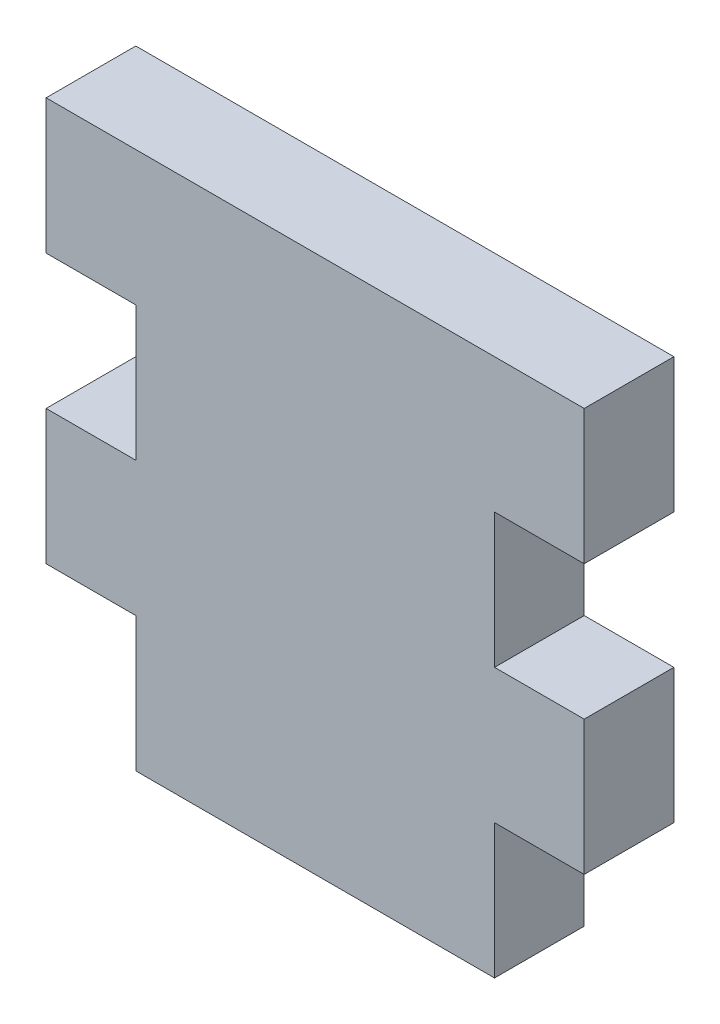
SolidWorks part; units mm, degrees
ref_plane "Front Plane" through (0, 0, 0) normal (0, 0, 1) x (1, 0, 0)
ref_plane "Top Plane" through (0, 0, 0) normal (0, 1, 0) x (1, 0, 0)
ref_plane "Right Plane" through (0, 0, 0) normal (1, 0, 0) x (0, 0, -1)
sketch "Sketch1" plane through (0, 0, 0) normal (0, 0, 1) x (1, 0, 0)
  line L1 (-88.0852, 14.1109) -> (-49.9852, 14.1109)
  line L2 (-88.0852, 14.1109) -> (-88.0852, -23.9891)
  line L3 (-88.0852, -23.9891) -> (-49.9852, -23.9891)
  line L4 (-49.9852, 14.1109) -> (-49.9852, -23.9891)
  dimension "D1" = 38.1
  dimension "D2" = 38.1
extrude "Boss-Extrude1" add sketch "Sketch1" along normal blind 6.35
sketch "Sketch2" plane through (0, 0, 6.35) normal (0, 0, 1) x (1, 0, 0)
  line L0 (-88.0852, 14.1109) -> (-88.0852, -23.9891) construction
  line L1 (-88.0852, -23.9891) -> (-81.7352, -23.9891)
  line L2 (-88.0852, -23.9891) -> (-88.0852, -14.4641)
  line L3 (-88.0852, -14.4641) -> (-81.7352, -14.4641)
  line L4 (-81.7352, -23.9891) -> (-81.7352, -14.4641)
  line L5 (-88.0852, -4.9391) -> (-81.7352, -4.9391)
  line L6 (-88.0852, -4.9391) -> (-88.0852, 4.5859)
  line L7 (-88.0852, 4.5859) -> (-81.7352, 4.5859)
  line L8 (-81.7352, -4.9391) -> (-81.7352, 4.5859)
  line L9 (-81.7352, 4.5859) -> (-81.7352, 14.1109) construction
  line L10 (-49.9852, 14.1109) -> (-88.0852, 14.1109) construction
  line L11 (-81.7352, -4.9391) -> (-81.7352, -14.4641) construction
  line L12 (-69.0352, 14.1109) -> (-69.0352, -23.9891) construction
  line L13 (-88.0852, -23.9891) -> (-49.9852, -23.9891) construction
  line L14 (-56.3352, -4.9391) -> (-56.3352, -14.4641) construction
  line L15 (-56.3352, 4.5859) -> (-56.3352, 14.1109) construction
  line L16 (-56.3352, -4.9391) -> (-56.3352, 4.5859)
  line L17 (-49.9852, 4.5859) -> (-56.3352, 4.5859)
  line L18 (-49.9852, -4.9391) -> (-49.9852, 4.5859)
  line L19 (-49.9852, -4.9391) -> (-56.3352, -4.9391)
  line L20 (-56.3352, -23.9891) -> (-56.3352, -14.4641)
  line L21 (-49.9852, -14.4641) -> (-56.3352, -14.4641)
  line L22 (-49.9852, -23.9891) -> (-49.9852, -14.4641)
  line L23 (-49.9852, -23.9891) -> (-56.3352, -23.9891)
  dimension "D1" = 6.35
extrude "Cut-Extrude1" cut sketch "Sketch2" against normal through all
equation "\"Mdf\" = .25in"
equation "\"Foamcore\" = .1875in"
equation "\"Gmaterial\"= \"Foamcore\""
equation "\"D1@Boss-Extrude1\"=\"MDF\""
equation "\"D1@Sketch2\"=\"MDF\""
equation "\"D2@Sketch1\"=\"MDF\"+\"MDF\"+1"
